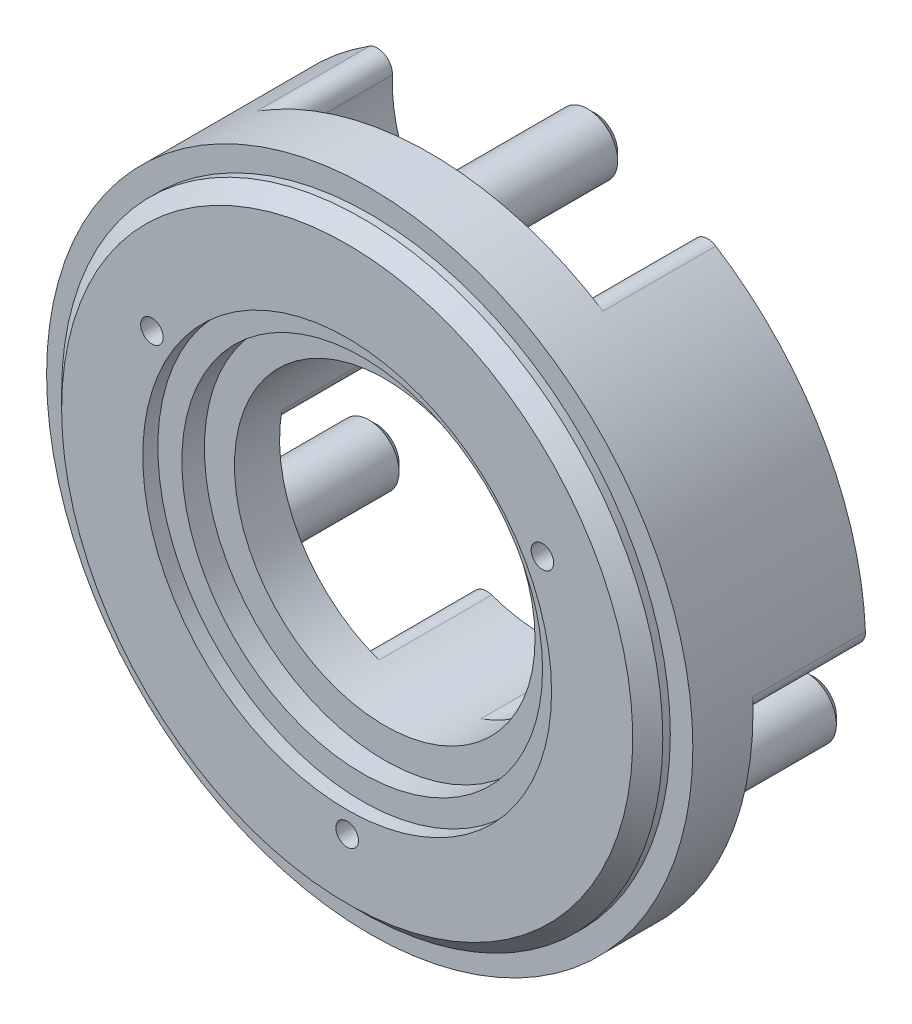
SolidWorks part; units mm, degrees
note: The reader was unsure of these and kept them because the rebuilt part matched: shared geometry of "Sketch7<3>".
ref_plane "Front Plane" through (0, 0, 0) normal (0, 0, 1) x (1, 0, 0)
ref_plane "Top Plane" through (0, 0, 0) normal (0, 1, 0) x (1, 0, 0)
ref_plane "Right Plane" through (0, 0, 0) normal (1, 0, 0) x (0, 0, -1)
sketch "Sketch3" plane through (0, 0, 0) normal (1, 0, 0) x (0, 0, -1)
  line L0 (0, 0) -> (0, 21.6269) construction
  line L1 (0, 0) -> (18.9047, 0) construction
  line L12 (1, 13.6) -> (1, 12)
  line L13 (0, 13.6) -> (1, 13.6)
  line L14 (1, 12) -> (2.5, 12)
  line L15 (2.5, 12) -> (2.5, 10)
  line L16 (2.5, 10) -> (5.5, 10)
  line L17 (5.5, 10) -> (5.5, 21.5)
  line L18 (5.5, 21.5) -> (1.5, 21.5)
  line L19 (1.5, 21.5) -> (1.5, 20)
  line L20 (1.5, 20) -> (0, 20)
  line L21 (0, 20) -> (0, 13.6)
  dimension "D1" = 13.6
  dimension "D2" = 12
  dimension "D3" = 10
  dimension "D4" = 21.5
  dimension "D5" = 20
  dimension "D6" = 3
  dimension "D7" = 5.5
  dimension "D8" = 1
  dimension "D9" = 2.5
revolve "Revolve1" add sketch "Sketch3" angle 360 about L1
sketch "Sketch4" plane through (0, 0, -5.5) normal (0, 0, -1) x (-1, 0, 0)
  circle A0 centre (0, 0) radius 15 construction
  circle A1 centre (0, 0) radius 21.5
  circle A2 centre (0, 0) radius 21.5
  circle A3 centre (0, 0) radius 16.8 construction
  circle A5 centre (0, 16.8) radius 4
  dimension "D2" = 30
  dimension "D3" = 33.6
  dimension "D4" = 8
  dimension "D1" = 0
extrude "Boss-Extrude1" add sketch "Sketch4" along normal blind 0.5 contours A5
sketch "Sketch5" plane through (0, 0, -6) normal (0, 0, -1) x (-1, 0, 0)
  circle A0 centre (0, 16.8) radius 2
  circle A1 centre (0, 16.8) radius 4
  circle A2 centre (0, 16.8) radius 4
  dimension "D2" = 4
  dimension "D1" = 0
extrude "Boss-Extrude2" add sketch "Sketch5" along normal blind 10.5 contours A0
chamfer "Chamfer1" distance 0.5 angle 45 1 edges at (-2, 16.8, -16.5)
pattern_circular "CirPattern1" count 3 over 360 about axis through (0, 0, 0) along (0, 0, 1) of "Chamfer1", "Boss-Extrude2", "Boss-Extrude1"
sketch "Sketch6" plane through (0, 0, -5.5) normal (0, 0, -1) x (-1, 0, 0)
  line L0 (0, 0) -> (0, -26.5877) construction
  line L1 (0, 0) -> (42.2681, 0) construction
  circle A1 centre (0, 0) radius 21.5
  circle A2 centre (0, 0) radius 21.5
  circle A3 centre (-14.5492, -8.4) radius 1.5
  circle A4 centre (-14.5492, -8.4) radius 1.5
  circle A5 centre (14.5492, -8.4) radius 1.5
  circle A6 centre (14.5492, -8.4) radius 1.5
  circle A9 centre (0, 0) radius 10 construction
  circle A10 centre (0, 0) radius 10
  arc A11 (-11.7553, -18.0018) -> (-4.5617, -8.8989) centre (-14.5492, -8.4) ccw
  arc A12 (4.5617, -8.8989) -> (11.7553, -18.0018) centre (14.5492, -8.4) ccw
  circle M11 centre (0, 0) radius 21.5
  dimension "D4" = 10
  dimension "D1" = 0
  dimension "D2" = 0
  dimension "D3" = 0
extrude "Boss-Extrude3" add sketch "Sketch6" along normal blind 7.5 contours A12 A10 A11 M11
sketch "Sketch7" plane through (0, 0, -13) normal (0, 0, -1) x (-1, 0, 0)
  line L2 (0, 0) -> (-4.6587, -17.3867)
  line L3 (4.6587, -17.3867) -> (0, 0)
  line L4 (0, 0) -> (0, -27.9066) construction
  arc A0 (-3.1058, -11.5911) -> (3.1058, -11.5911) centre (0, 0) ccw
  arc A1 (-4.6587, -17.3867) -> (4.6587, -17.3867) centre (0, 0) ccw
  circle A2 centre (0, -15) radius 0.75
  dimension "D1" = 18
  dimension "D2" = 12
  dimension "D5" = 1.5
  dimension "D3" = 30
  dimension "D4" = 15
  dimension "D6" = 15
extrude "Cut-Extrude1" cut sketch "Sketch7" against normal blind 2 contours A0 L4 A1 L3 | L4 A0 L2 A1
extrude "Cut-Extrude2" cut sketch "Sketch7<3>" against normal through all contours A2 L4 | L4 A2
sketch "Sketch7<3>" plane through (0, 0, -13) normal (0, 0, -1) x (-1, 0, 0) same geometry as "Sketch7"
chamfer "Chamfer2" distance 0.2 angle 45 1 edges at (-0.75, -15, -11)
chamfer "Chamfer3" distance 0.5 angle 45 4 edges at (0, -18, -13) (3.8823, -14.4889, -13) (0, -12, -13) (-3.8823, -14.4889, -13)
pattern_circular "CirPattern2" count 3 over 360 about axis through (0, 0, 0) along (0, 0, 1) of "Chamfer3", "Chamfer2", "Cut-Extrude2", "Cut-Extrude1", "Boss-Extrude3"
chamfer "Chamfer4" distance 1 angle 45 1 edges at (20, 0, 0)
fillet "Fillet1" radius 1 12 edges at (21.4676, -1.1795, -9.25) (9.9875, 0.4989, -9.25) (5.4259, 8.4, -9.25) (9.7123, 19.1813, -9.25) (-9.7123, 19.1812, -9.25) (-5.4259, 8.4, -9.25) (-9.9875, 0.4989, -9.25) (-21.4676, -1.1795, -9.25) (-11.7553, -18.0018, -9.25) (-4.5617, -8.8989, -9.25) (4.5617, -8.8989, -9.25) (11.7553, -18.0018, -9.25)
